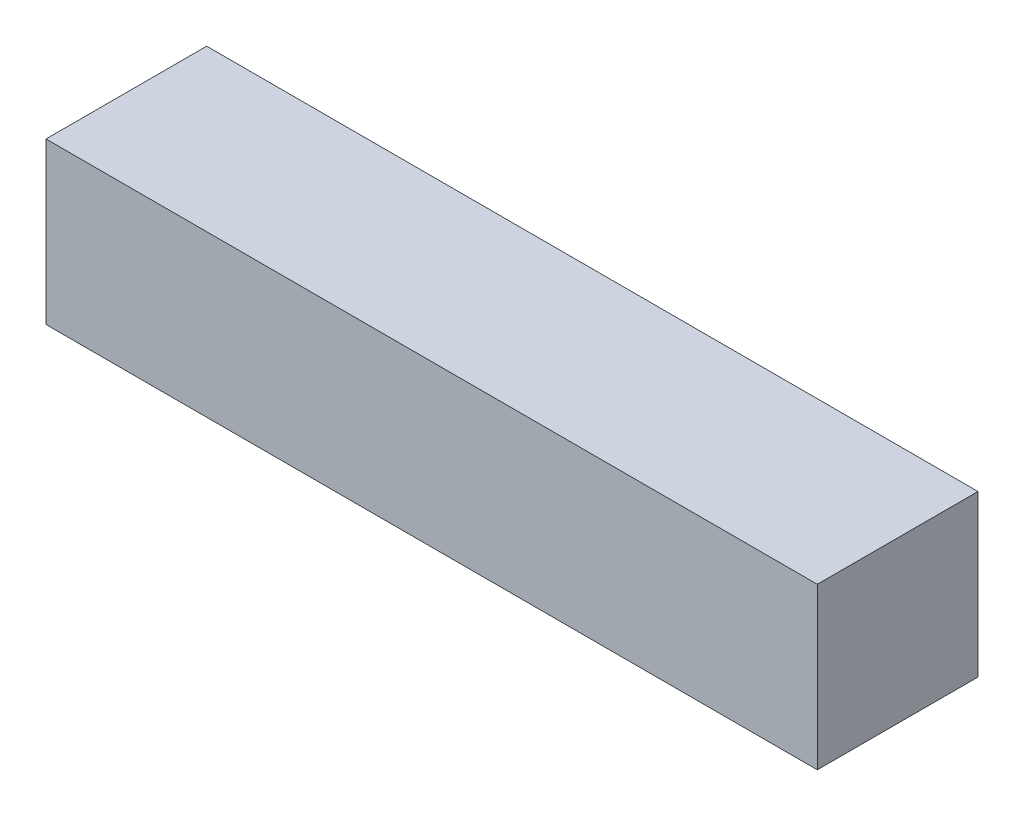
SolidWorks part; units mm, degrees
ref_plane "Front Plane" through (0, 0, 0) normal (0, 0, 1) x (1, 0, 0)
ref_plane "Top Plane" through (0, 0, 0) normal (0, 1, 0) x (1, 0, 0)
ref_plane "Right Plane" through (0, 0, 0) normal (1, 0, 0) x (0, 0, -1)
sketch "Sketch1" plane through (0, 0, 0) normal (0, 0, 1) x (1, 0, 0)
  line L0 (0, 0) -> (0, 309.1855) construction
  line L1 (-600, 0) -> (600, 0)
  line L2 (-600, 0) -> (-600, 250)
  line L3 (-600, 250) -> (600, 250)
  line L4 (600, 0) -> (600, 250)
  dimension "D1" = 1200
  dimension "D2" = 250
extrude "Boss-Extrude1" add sketch "Sketch1" along normal mid plane 250
ref_axis "Axis1" through (0, 324.6448, 0) along (0, -1, 0)
